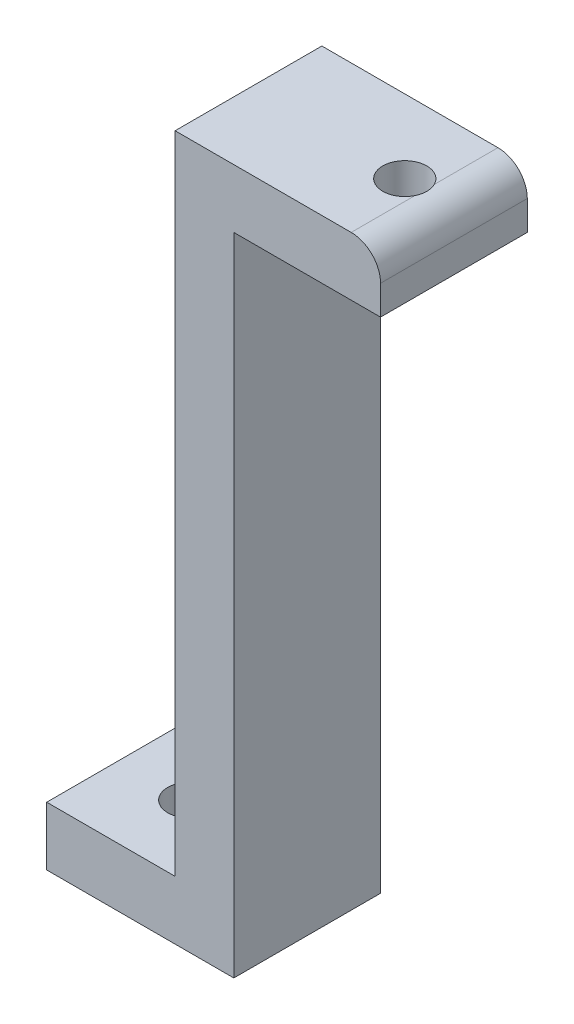
SolidWorks part; units mm, degrees
ref_plane "Front Plane" through (0, 0, 0) normal (0, 0, 1) x (1, 0, 0)
ref_plane "Top Plane" through (0, 0, 0) normal (0, 1, 0) x (1, 0, 0)
ref_plane "Right Plane" through (0, 0, 0) normal (1, 0, 0) x (0, 0, -1)
sketch "Sketch1" plane through (0, 0, 0) normal (0, 0, 1) x (1, 0, 0)
  line L0 (0, 0) -> (-14, 0)
  line L1 (-14, 0) -> (-14, -44)
  line L2 (-14, -44) -> (-22.75, -44)
  line L3 (-22.75, -44) -> (-22.75, -48)
  line L4 (-22.75, -48) -> (-10, -48)
  line L5 (-10, -48) -> (-10, -4)
  line L6 (-10, -4) -> (0, -4)
  line L7 (0, -4) -> (0, 0)
  dimension "D1" = 4
  dimension "D2" = 4
  dimension "D3" = 4
  dimension "D4" = 44
  dimension "D5" = 12.75
  dimension "D6" = 10
extrude "Boss-Extrude1" add sketch "Sketch1" along normal blind 10
sketch "Sketch2" plane through (0, -44, 0) normal (0, 1, 0) x (1, 0, 0)
  line L0 (-22.75, -10) -> (-22.75, 0) construction
  circle A0 centre (-18, -5) radius 1.5
  point P4 (-22.75, -5)
  dimension "D1" = 3
  dimension "D2" = 4.75
  dimension "D3" = 0
extrude "Cut-Extrude1" cut sketch "Sketch2" against normal blind 10
sketch "Sketch3" plane through (0, -4, 0) normal (0, -1, 0) x (-1, 0, 0)
  line L0 (0, -10) -> (0, 0) construction
  line L2 (10, -10) -> (10, 0) construction
  circle A0 centre (3.35, -5) radius 1.5
  point P4 (0, -5)
  dimension "D1" = 3
  dimension "D2" = 0
  dimension "D3" = 6.65
extrude "Cut-Extrude2" cut sketch "Sketch3" against normal blind 10
fillet "Fillet1" radius 2 1 edges at (0, 0, 5)
